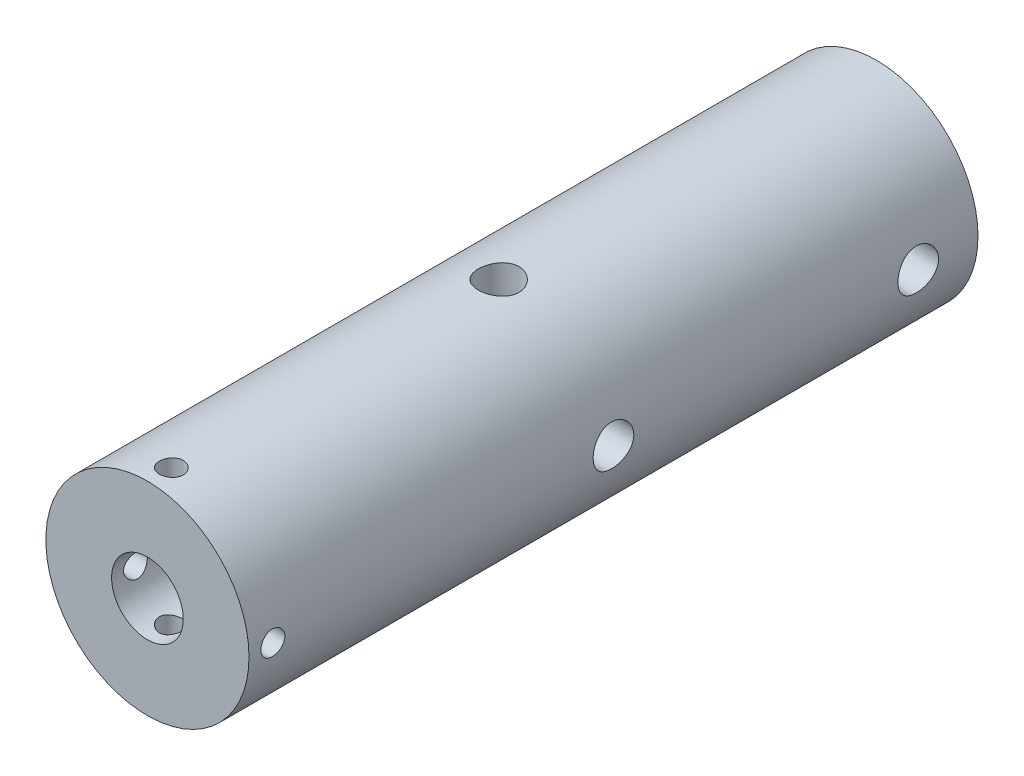
SolidWorks part; units mm, degrees
material "Alumina"
ref_plane "Front Plane" through (0, 0, 0) normal (0, 0, 1) x (1, 0, 0)
ref_plane "Top Plane" through (0, 0, 0) normal (0, 1, 0) x (1, 0, 0)
ref_plane "Right Plane" through (0, 0, 0) normal (1, 0, 0) x (0, 0, -1)
sketch "Sketch1" plane through (0, 0, 0) normal (0, 0, 1) x (1, 0, 0)
  circle A0 centre (0, 0) radius 8.5
  dimension "D1" = 17
extrude "Boss-Extrude1" add sketch "Sketch1" along normal blind 61
ref_plane "Plane1" through (0, 0, 0) normal (1, 0, 0) x (0, 0, -1)
ref_plane "Plane2" through (0, 0, 61) normal (0, 0, 1) x (1, 0, 0)
sketch "Sketch7" plane through (0, 0, 0) normal (1, 0, 0) x (0, 0, -1)
  line L0 (0, 0) -> (-64.6099, 0) construction
  line L1 (-64.6099, 0) -> (5.371, 0) construction
  line L2 (-61, 3) -> (-5, 3)
  line L3 (-61, 8.5) -> (-61, -8.5) construction
  line L4 (-5, 3) -> (-1, 1.5)
  line L5 (-1, 1.5) -> (0, 1.5)
  line L6 (0, -8.5) -> (0, 8.5) construction
  line L7 (0, 1.5) -> (0, 0)
  line L8 (-61, 3) -> (-61, 0)
  line L9 (0, 0) -> (-61, 0)
  point P8 (-0.5, 1.5)
  dimension "D1" = 4
  dimension "D2" = 1
  dimension "D3" = 1.5
  dimension "D4" = 3
revolve "Cut-Revolve1" cut sketch "Sketch7" angle 360 about L0
ref_plane "Plane3" through (8.5, 0, 0) normal (1, 0, 0) x (0, 0, -1)
sketch "Sketch9" plane through (8.5, 0, 0) normal (1, 0, 0) x (0, 0, -1)
  circle A0 centre (-5, 0) radius 1.7
  dimension "D1" = 3.4
  dimension "D2" = 5
extrude "Cut-Extrude2" cut sketch "Sketch9" against normal blind 6.7
sketch "Sketch10" plane through (0, 0, 0) normal (1, 0, 0) x (0, 0, -1)
  line L0 (-61, 8.5) -> (-61, -8.5) construction
  circle A0 centre (-59, 0) radius 1
  dimension "D1" = 2
  dimension "D2" = 2
extrude "Cut-Extrude3" cut sketch "Sketch10" against normal blind 8.7
pattern_circular "CirPattern1" count 4 over 360 about axis through (0, 0, 61) along (0, 0, 1) of "Cut-Extrude3"
ref_plane "Plane4" through (0, 8.5, 0) normal (0, 1, 0) x (1, 0, 0)
sketch "Sketch11" plane through (0, 8.5, 0) normal (0, 1, 0) x (1, 0, 0)
  line L0 (0, 0) -> (0, -63.2228) construction
  line L1 (0, -63.2228) -> (0, -31.6114) construction
  line L2 (0, -31.6114) -> (12.403, -31.6114) construction
  line L3 (12.403, -31.6114) -> (-11.7433, -31.6114) construction
  circle A0 centre (0, -31.6114) radius 1.7
  dimension "D1" = 3.4
extrude "Cut-Extrude4" cut sketch "Sketch11" against normal blind 8.7
sketch "Sketch12" plane through (0, 0, 0) normal (1, 0, 0) x (0, 0, -1)
  line L0 (0, 0) -> (-61, 0) construction
  line L1 (-61, 8.5) -> (-61, -8.5) construction
  line L2 (-61, 0) -> (-30.5, 0) construction
  circle A0 centre (-30.5, 0) radius 1.7
  dimension "3" = 3.4
extrude "Cut-Extrude5" cut sketch "Sketch12" against normal blind 10 and the other way blind 10
